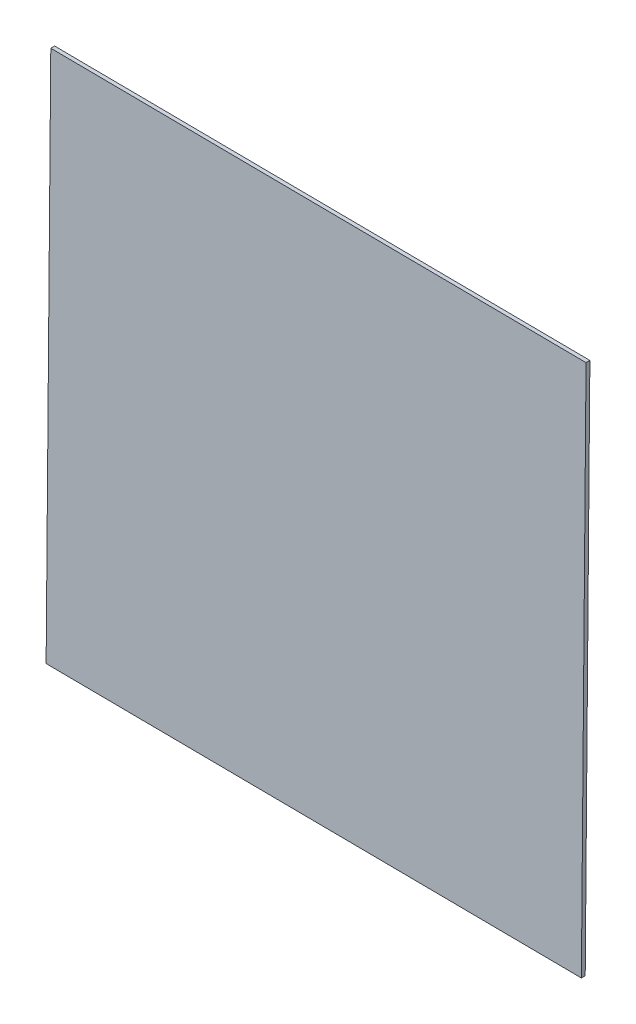
SolidWorks part; units mm, degrees
ref_plane "Front Plane" through (0, 0, 0) normal (0, 0, 1) x (1, 0, 0)
ref_plane "Top Plane" through (0, 0, 0) normal (0, 1, 0) x (1, 0, 0)
ref_plane "Right Plane" through (0, 0, 0) normal (1, 0, 0) x (0, 0, -1)
sketch "Sketch1" plane through (0, 0, 0) normal (0, 0, 1) x (1, 0, 0)
  line L4 (-97.7146, 56.2371) -> (-79.9861, 56.0824)
  line L5 (-79.9861, 56.0824) -> (-79.8314, 73.8109)
  line L6 (-79.8314, 73.8109) -> (-97.5599, 73.9656)
  line L7 (-97.5599, 73.9656) -> (-97.7146, 56.2371)
  line L8 (-97.7146, 56.2371) -> (-79.9861, 56.0824)
  line L9 (-79.9861, 56.0824) -> (-79.8314, 73.8109)
  line L10 (-79.8314, 73.8109) -> (-97.5599, 73.9656)
  line L11 (-97.5599, 73.9656) -> (-97.7146, 56.2371)
  dimension "D1" = 0
extrude "Boss-Extrude1" add sketch "Sketch1" along normal blind 0.127
sketch "Sketch2" plane through (0, 0, 0) normal (0, 0, -1) x (-1, 0, 0)
  line L0 (97.6376, 65.024) -> (79.9084, 65.024) construction
  line L1 (79.9861, 56.0824) -> (79.8314, 73.8109) construction
  line L2 (97.5599, 73.9656) -> (97.7146, 56.2371) construction
  line L3 (79.9084, 57.1754) -> (97.6376, 57.1754) construction
  line L4 (79.9328, 62.1919) -> (97.6627, 62.1919) construction
  line L7 (86.233, 57.1754) -> (89.1133, 57.1754)
  line L8 (89.1133, 57.1754) -> (91.313, 60.9854)
  line L9 (91.313, 60.9854) -> (88.4327, 60.9854)
  line L10 (88.4327, 60.9854) -> (86.233, 57.1754)
  line L11 (88.773, 73.8886) -> (88.773, 56.1594) construction
  line L14 (81.4477, 57.1754) -> (84.328, 57.1754)
  line L15 (84.328, 57.1754) -> (86.5277, 60.9854)
  line L16 (86.5277, 60.9854) -> (83.6474, 60.9854)
  line L17 (83.6474, 60.9854) -> (81.4477, 57.1754)
  line L18 (91.0183, 57.1754) -> (93.218, 60.9854)
  line L19 (93.218, 60.9854) -> (96.0983, 60.9854)
  line L20 (96.0983, 60.9854) -> (93.8986, 57.1754)
  line L21 (93.8986, 57.1754) -> (91.0183, 57.1754)
  line L22 (79.9084, 72.8726) -> (97.6376, 72.8726) construction
  line L23 (86.233, 69.0626) -> (89.1133, 69.0626)
  line L24 (89.1133, 69.0626) -> (91.313, 72.8726)
  line L25 (91.313, 72.8726) -> (88.4327, 72.8726)
  line L26 (88.4327, 72.8726) -> (86.233, 69.0626)
  line L27 (81.4477, 69.0626) -> (84.328, 69.0626)
  line L28 (84.328, 69.0626) -> (86.5277, 72.8726)
  line L29 (86.5277, 72.8726) -> (83.6474, 72.8726)
  line L30 (83.6474, 72.8726) -> (81.4477, 69.0626)
  line L31 (91.0183, 69.0626) -> (93.218, 72.8726)
  line L32 (93.218, 72.8726) -> (96.0983, 72.8726)
  line L33 (96.0983, 72.8726) -> (93.8986, 69.0626)
  line L34 (93.8986, 69.0626) -> (91.0183, 69.0626)
  line L35 (87.6731, 57.1754) -> (89.8729, 60.9854) construction
  text T0 "<b>FIRE</b>" font "GordonURWMed" height in points 24
  point P18 (87.6731, 57.1754)
  point P26 (89.8729, 60.9854)
  point P40 (87.6731, 69.0626)
  point P43 (89.8729, 72.8726)
  point P53 (88.773, 59.0804)
  dimension "D1" = 2.8321
wrap "FIRE" [suppressed] sketch "Sketch2" source sketch "Sketch2"
sketch "Sketch3" plane through (0, 0, 0) normal (0, 0, -1) x (-1, 0, 0)
  line L0 (79.9084, 65.3056) -> (97.6376, 65.3056) construction
  line L3 (79.9084, 65.024) -> (97.6376, 65.024) construction
  line L4 (79.9084, 60.5059) -> (97.6376, 60.5059) construction
  line L5 (79.9084, 69.5421) -> (97.6376, 69.5421) construction
  line L6 (95.8049, 69.5421) -> (95.8049, 60.5059) construction
  text T0 "APU" font "GordonURWMed" height in points 18
  text T1 "FIRE" font "GordonURWMed" height in points 18
  point P15 (95.8049, 65.024)
wrap "APU FIRE" [suppressed] sketch "Sketch3" source sketch "Sketch3"
sketch "Sketch4" plane through (0, 0, 0) normal (0, 0, -1) x (-1, 0, 0)
  line L0 (79.9084, 65.4564) -> (97.6376, 65.4564) construction
  line L4 (79.9084, 65.024) -> (97.6376, 65.024) construction
  line L6 (79.9084, 61.4926) -> (97.6376, 61.4926) construction
  text T0 "MASTER" font "GordonURWCon" height in points 14
  text T1 "CAUTION" font "GordonURWCon" height in points 14
wrap "MC" sketch "Sketch4" wrap type scribe source sketch "Sketch4" face at (-88.773, 65.024, 0)
